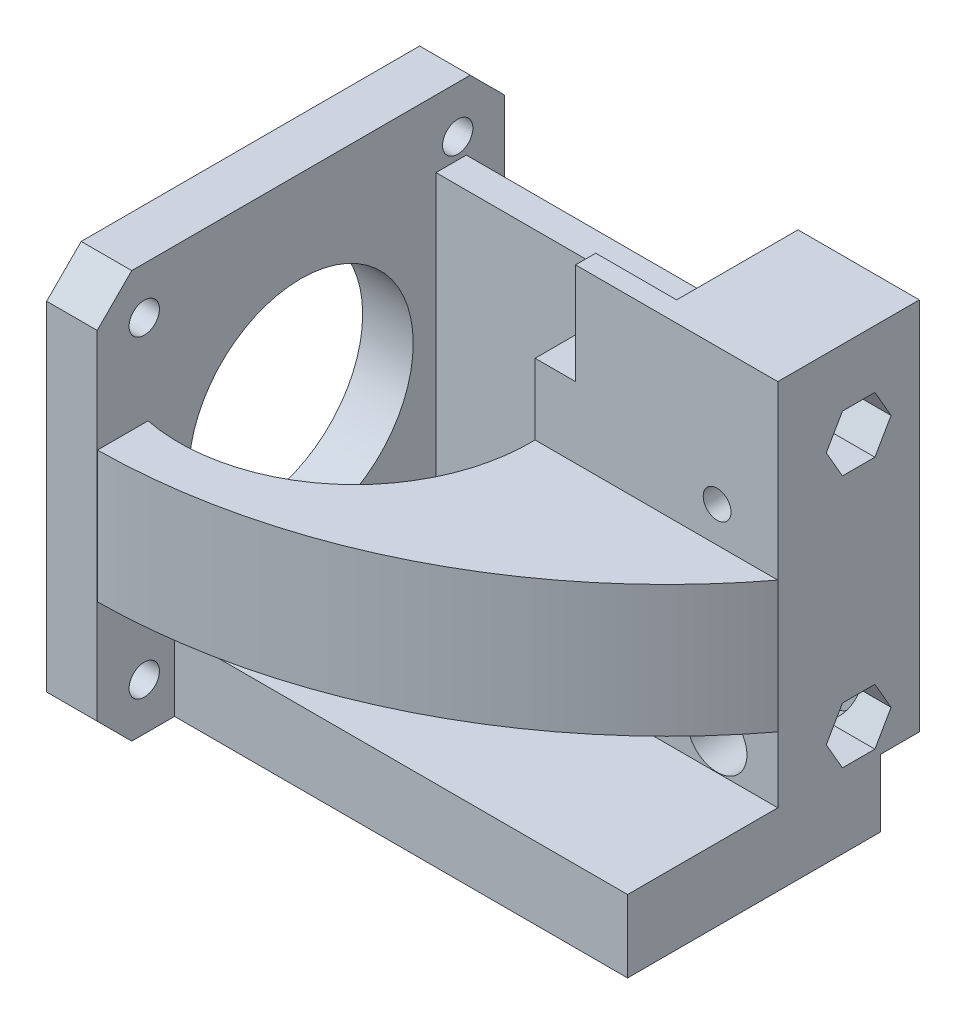
SolidWorks part; units mm, degrees
note: The reader was unsure of these and kept them because the rebuilt part matched: shared geometry of "Sketch1<3>", "Sketch1<4>", "Sketch10<4>", "Sketch13<6>", "Sketch13<7>".
ref_plane "Front Plane" through (0, 0, 0) normal (0, 0, 1) x (1, 0, 0)
ref_plane "Top Plane" through (0, 0, 0) normal (0, 1, 0) x (1, 0, 0)
ref_plane "Right Plane" through (0, 0, 0) normal (1, 0, 0) x (0, 0, -1)
sketch "Sketch1" plane through (0, 0, 0) normal (0, 0, 1) x (1, 0, 0)
  line L0 (-4, -21.9999) -> (-4, 427.0001) construction
  line L1 (16, -13.5) -> (-16, -13.5)
  line L2 (16, -13.5) -> (16, 13.5)
  line L3 (16, 13.5) -> (-16, 13.5)
  line L4 (-16, -13.5) -> (-16, 13.5)
  line L5 (4, -13.5) -> (-4, -13.5)
  line L6 (4, -13.5) -> (4, 13.5)
  line L7 (4, 13.5) -> (-4, 13.5)
  line L8 (-4, -13.5) -> (-4, 13.5)
  line L9 (4, 427.0001) -> (4, -21.9999) construction
  line L10 (-16, 13.5) -> (16, 13.5) construction
  line L11 (-16, 5.5) -> (-16, -6.25) construction
  line L12 (16, -6.25) -> (16, 5.5) construction
  line L14 (16, -13.5) -> (-16, -13.5) construction
  circle A0 centre (-10, -10) radius 1.375
  circle A1 centre (-10, 10) radius 1.375
  circle A2 centre (10, 10) radius 1.375
  circle A3 centre (10, -10) radius 1.35
extrude "Boss-Extrude1" add sketch "Sketch1" along normal blind 3 contours L1 L8 L3 L4 A1 A0 | L6 L1 L2 L3 A3 A2
sketch "Sketch2" plane through (-33.8, 0, 0) normal (1, 0, 0) x (0, 0, -1)
  line L0 (0.3848, -20.15) -> (3.799, -16.7358)
  line L1 (3.799, -16.7358) -> (3.799, 16.7358)
  line L2 (3.799, 16.7358) -> (0.3848, 20.15)
  line L3 (0.3848, 20.15) -> (-33.0868, 20.15)
  line L4 (-33.0868, 20.15) -> (-36.501, 16.7358)
  line L5 (-36.501, 16.7358) -> (-36.501, -16.7358)
  line L6 (-36.501, -16.7358) -> (-33.0868, -20.15)
  line L7 (-33.0868, -20.15) -> (0.3848, -20.15)
  circle A0 centre (-31.851, -15.5) radius 1.5
  circle A1 centre (-0.851, -15.5) radius 1.5
  circle A2 centre (-0.851, 15.5) radius 1.5
  circle A3 centre (-31.851, 15.5) radius 1.5
  circle A4 centre (-16.351, 0) radius 11.1
  dimension "D1" = 3
  dimension "D2" = 3
  dimension "D3" = 3
  dimension "D4" = 3
  dimension "D5" = 22.2
extrude "Boss-Extrude2" add sketch "Sketch2" along normal blind 5 separate body
sketch "Sketch4" plane through (0, 0, 3) normal (0, 0, 1) x (1, 0, 0)
  line L0 (-4, 13.5) -> (-16, 13.5) construction
  line L1 (-16, -13.5) -> (-28.8, -13.5)
  line L2 (-16, -13.5) -> (-16, 13.5)
  line L3 (-16, 13.5) -> (-28.8, 13.5)
  line L4 (-28.8, -13.5) -> (-28.8, 13.5)
  line L5 (-28.8, 16.7358) -> (-28.8, -16.7358) construction
extrude "Boss-Extrude3" add sketch "Sketch4" against normal up to surface (3 mm away)
extrude "Boss-Extrude4" add sketch "Sketch1<3>" along normal up to surface (12 mm away) contours L6 L1 L2 L3 A3 A2
sketch "Sketch1<3>" plane through (0, 0, 0) normal (0, 0, 1) x (1, 0, 0) same geometry as "Sketch1"
sketch "Sketch5" plane through (0, 0, 3) normal (0, 0, 1) x (1, 0, 0)
  line L0 (-4, 13.5) -> (-28.8, 13.5) construction
  line L1 (-4, -13.5) -> (-8, -13.5)
  line L2 (-4, -13.5) -> (-4, 13.5)
  line L3 (-4, 13.5) -> (-8, 13.5)
  line L4 (-8, -13.5) -> (-8, 13.5)
  dimension "D1" = 4
extrude "Boss-Extrude5" add sketch "Sketch5" along normal up to surface (9 mm away)
sketch "Sketch6" plane through (0, 0, 12) normal (0, 0, 1) x (1, 0, 0)
  line L1 (-8, -13.5) -> (16, -13.5)
  line L2 (-8, -13.5) -> (-8, 13.5)
  line L3 (-8, 13.5) -> (16, 13.5)
  line L4 (16, -13.5) -> (16, 13.5)
extrude "Boss-Extrude6" add sketch "Sketch6" along normal blind 2
extrude "Cut-Extrude3" cut sketch "Sketch1<4>" along normal through all contours A3 | A2
sketch "Sketch1<4>" plane through (0, 0, 0) normal (0, 0, 1) x (1, 0, 0) same geometry as "Sketch1"
sketch "Sketch10" plane through (0, 0, 14) normal (0, 0, 1) x (1, 0, 0)
  line L0 (-4, -21.9999) -> (-4, 427.0001) construction
  line L1 (16, 13.5) -> (-4, 13.5)
  line L2 (16, 13.5) -> (16, 23.5)
  line L3 (16, 23.5) -> (-4, 23.5)
  line L4 (-4, 13.5) -> (-4, 23.5)
  line L5 (4, 427.0001) -> (4, -21.9999) construction
  line L6 (16, 13.5) -> (4, 13.5)
  line L7 (16, 13.5) -> (16, 23.5)
  line L8 (16, 23.5) -> (4, 23.5)
  line L9 (4, 13.5) -> (4, 23.5)
  line M9 (16, 13.5) -> (-8, 13.5)
  dimension "D1" = 10
extrude "Boss-Extrude7" add sketch "Sketch10" against normal up to surface (2 mm away) contours L1 L9 L3 L4
extrude "Boss-Extrude8" add sketch "Sketch10<4>" against normal up to vertex (15 mm away) contours L9 L2 L3 M9
sketch "Sketch10<4>" plane through (0, 0, 14) normal (0, 0, 1) x (1, 0, 0) same geometry as "Sketch10"
sketch "Sketch8" plane through (4, 0, 0) normal (1, 0, 0) x (0, 0, -1)
  circle A0 centre (-6, -9.9999) radius 1.5
  circle A1 centre (-6, 15.0001) radius 1.5
  dimension "D1" = 3
  dimension "D2" = 3
extrude "Cut-Extrude4" cut sketch "Sketch8" along normal through all and the other way up to surface contours A1 | A0 other way up to face at (-8, 0, 8.5)
sketch "Sketch11" plane through (-8, 0, 0) normal (-1, 0, 0) x (0, 0, 1)
  circle A0 centre (6, -9.9999) radius 3
  circle A1 centre (6, 15.0001) radius 3
  dimension "D1" = 6
  dimension "D2" = 6
extrude "Cut-Extrude5" cut sketch "Sketch11" against normal up to surface (8 mm away)
sketch "Sketch12" plane through (0, -13.5, 0) normal (0, -1, 0) x (1, 0, 0)
  line L4 (-28.8, 36.501) -> (-33.8, 36.501) construction
  line L5 (-28.7768, 36.501) -> (-28.7768, 31.501)
  line L6 (-8, 14) -> (16, 14)
  arc A0 (16, 14) -> (-28.7768, 36.501) centre (-29.3174, -20.378) ccw
  arc A1 (-8, 14) -> (-28.7768, 31.501) centre (-25.3897, 14.4387) ccw
  dimension "D1" = 5
  dimension "D2" = 0
extrude "Boss-Extrude9" add sketch "Sketch12" against normal blind 13 from offset 7 offset against normal yes
sketch "Sketch13" plane through (-28.8, 0, 0) normal (1, 0, 0) x (0, 0, -1)
  line L8 (-33.0868, -20.15) -> (0.3848, -20.15) construction
  line L10 (-28.851, -20.15) -> (-3.851, -20.15)
  line L12 (-28.851, -20.15) -> (-28.851, -13.5)
  line L13 (-28.851, -13.5) -> (-3.851, -13.5)
  line L14 (-3.851, -20.15) -> (-3.851, -13.5)
  line L15 (0, -13.5) -> (-3, -13.5) construction
  line L16 (-12, 427.0001) -> (-12, -21.9999) construction
  line L17 (-3.851, -13.5) -> (-12, -13.5)
  line L18 (-3.851, -13.5) -> (-3.851, -20.15)
  line L19 (-3.851, -20.15) -> (-12, -20.15)
  line L20 (-12, -13.5) -> (-12, -20.15)
  circle A2 centre (-31.851, -15.5) radius 1.5 construction
  circle A4 centre (-0.851, -15.5) radius 1.5 construction
  line M17 (-33.0868, -20.15) -> (0.3848, -20.15)
  dimension "D1" = 3
  dimension "D2" = 3
extrude "Boss-Extrude14" add sketch "Sketch13" along normal up to surface (24.8 mm away) separate body contours L20 L13 L12 M17 | L13 L20 L10 L14
extrude "Boss-Extrude15" add sketch "Sketch13<6>" along normal up to surface (44.8 mm away) contours L20 L13 L12 M17 up to face at (16, 15.0001, 4.5)
sketch "Sketch13<6>" plane through (-28.8, 0, 0) normal (1, 0, 0) x (0, 0, -1) same geometry as "Sketch13"
extrude "Boss-Extrude16" add sketch "Sketch13<7>" against normal up to surface (12 mm away) from surface contours L13 L20 L10 L14
sketch "Sketch13<7>" plane through (-28.8, 0, 0) normal (1, 0, 0) x (0, 0, -1) same geometry as "Sketch13"
sketch "Sketch14" plane through (-28.8, 0, 0) normal (1, 0, 0) x (0, 0, -1)
  line L0 (-3.851, -20.15) -> (-3.851, -13.5)
  line L1 (-3.851, -13.5) -> (3.799, -13.5)
  line L2 (3.799, -16.7358) -> (3.799, 16.7358) construction
  line L3 (3.799, -13.5) -> (3.799, -16.7358)
  line L4 (3.799, -16.7358) -> (0.3848, -20.15)
  line L5 (0.3848, -20.15) -> (-3.851, -20.15)
  circle A0 centre (-0.851, -15.5) radius 3
  circle M20 centre (-0.851, -15.5) radius 1.5
  line M23 (0, 13.5) -> (0, -13.5)
  line M24 (0, -13.5) -> (-3, -13.5)
  line M25 (-3, -13.5) -> (-3, 13.5)
  dimension "D1" = 6
sketch "Sketch16" plane through (0, 0, 3) normal (0, 0, 1) x (1, 0, 0)
  line L1 (-28.8, -13.5) -> (16, -13.5)
  line L2 (-28.8, -13.5) -> (-28.8, -13)
  line L3 (-28.8, -13) -> (16, -13)
  line L4 (16, -13.5) -> (16, -13)
  line L6 (16, -13.5) -> (16, -6.5) construction
  circle A0 centre (-10, -10) radius 1.375 construction
  dimension "D1" = 3
extrude "Boss-Extrude18" add sketch "Sketch16" along normal up to surface (25.851 mm away) up to face at (-6.4, -16.825, 28.851)
extrude "Cut-Extrude8" cut sketch "Sketch14" along normal blind 8 contours L1 A0 M24 M20 | L1 A0 M23 | A0 M23 M25 M24
sketch "Sketch17" plane through (16, 0, 0) normal (1, 0, 0) x (0, 0, -1)
  line L0 (-9.2043, -9.9999) -> (-7.6021, -7.2249)
  line L1 (-7.6021, -7.2249) -> (-4.3979, -7.2249)
  line L2 (-4.3979, -7.2249) -> (-2.7957, -9.9999)
  line L3 (-2.7957, -9.9999) -> (-4.3979, -12.7749)
  line L4 (-4.3979, -12.7749) -> (-7.6021, -12.7749)
  line L5 (-7.6021, -12.7749) -> (-9.2043, -9.9999)
  line L6 (-4.3979, -12.7749) -> (-7.6021, -7.2249) construction
  line L7 (-2.7957, -9.9999) -> (-9.2043, -9.9999) construction
  line L8 (-7.6021, -12.7749) -> (-4.3979, -7.2249) construction
  line L9 (-9.2043, 15.0001) -> (-7.6021, 17.7751)
  line L10 (-7.6021, 17.7751) -> (-4.3979, 17.7751)
  line L11 (-4.3979, 17.7751) -> (-2.7957, 15.0001)
  line L12 (-2.7957, 15.0001) -> (-4.3979, 12.2251)
  line L13 (-4.3979, 12.2251) -> (-7.6021, 12.2251)
  line L14 (-7.6021, 12.2251) -> (-9.2043, 15.0001)
  line L15 (-4.3979, 12.2251) -> (-7.6021, 17.7751) construction
  line L16 (-2.7957, 15.0001) -> (-9.2043, 15.0001) construction
  line L17 (-7.6021, 12.2251) -> (-4.3979, 17.7751) construction
  circle A0 centre (-6, 15.0001) radius 1.5 construction
  circle A3 centre (-6, -9.9999) radius 1.5 construction
  point P2 (-6, -9.9999)
  point P9 (-6, 15.0001)
  dimension "D1" = 120
  dimension "D2" = 120
  dimension "D3" = 5.55
  dimension "D4" = 120
  dimension "D5" = 120
  dimension "D6" = 5.55
extrude "Cut-Extrude9" cut sketch "Sketch17" against normal blind 11
sketch "Sketch18" plane through (0, 0, 14) normal (0, 0, 1) x (1, 0, 0)
  circle A0 centre (10, -10) radius 2.95
  dimension "D1" = 5.9
extrude "Cut-Extrude14" cut sketch "Sketch18" against normal up to vertex
